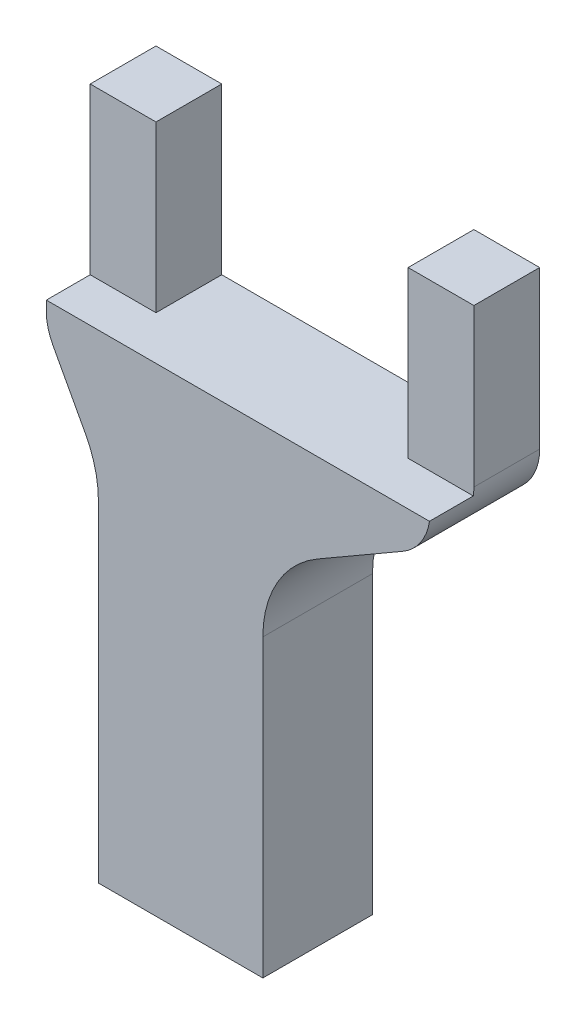
SolidWorks part; units mm, degrees
ref_plane "Front Plane" through (0, 0, 0) normal (0, 0, 1) x (1, 0, 0)
ref_plane "Top Plane" through (0, 0, 0) normal (0, 1, 0) x (1, 0, 0)
ref_plane "Right Plane" through (0, 0, 0) normal (1, 0, 0) x (0, 0, -1)
sketch "Sketch1" plane through (0, 0, 0) normal (0, 0, 1) x (1, 0, 0)
  line L0 (-7.5, 465.3207) -> (-7.5, 488.0002) construction
  line L2 (-7.5, 467.3207) -> (-7.5, 500.038)
  line L3 (-6.25, 511.0002) -> (16.75, 511.0002)
  line L4 (7.5, 467.3207) -> (7.5, 500.038)
  line L5 (7.5, 488.0002) -> (7.5, 465.3207) construction
  line L6 (5.5, 467.3207) -> (-5.5, 467.3207) construction
  line L7 (7.5, 467.3207) -> (-7.5, 467.3207)
  line L9 (-6.25, 526.0712) -> (-6.25, 511.0002)
  line L11 (16.75, 526.0712) -> (16.75, 511.0002)
  line L12 (16.5, 512.5012) -> (16.5, 524.8512) construction
  line L13 (-6, 512.5012) -> (-6, 524.8512) construction
  line L15 (22.75, 526.0712) -> (22.75, 508.8426)
  line L16 (22.75, 508.8426) -> (7.5, 500.038)
  line L17 (16.75, 526.0712) -> (22.75, 526.0712)
  line L18 (-6.25, 526.0712) -> (-12.25, 526.0712)
  line L19 (-12.25, 526.0712) -> (-12.25, 508.8426)
  line L20 (-12.25, 508.8426) -> (-7.5, 500.038)
  circle A0 centre (0, 491.0002) radius 1 construction
  dimension "D1" = 0
  dimension "D2" = 20
  dimension "D3" = 0.25
  dimension "D4" = 0.25
  dimension "D5" = 6
  dimension "D6" = 6
extrude "Boss-Extrude1" add sketch "Sketch1" along normal blind 10
fillet "Fillet1" radius 10 2 edges at (-7.5, 500.038, 5) (7.5, 500.038, 5)
fillet "Fillet2" radius 5 2 edges at (-12.25, 508.8426, 5) (22.75, 508.8426, 5)
sketch "Sketch2" plane through (0, 0, 10) normal (0, 0, 1) x (1, 0, 0)
  line L0 (16.75, 511.0002) -> (-6.25, 511.0002) construction
  line L1 (-12.25, 526.0712) -> (22.75, 526.0712)
  line L2 (-12.25, 526.0712) -> (-12.25, 511.0002)
  line L3 (-12.25, 511.0002) -> (22.75, 511.0002)
  line L4 (22.75, 526.0712) -> (22.75, 511.0002)
  line L5 (22.75, 511.7293) -> (22.75, 526.0712) construction
  dimension "D1" = 0
  dimension "D2" = 0
extrude "Cut-Extrude1" cut sketch "Sketch2" against normal blind 4
